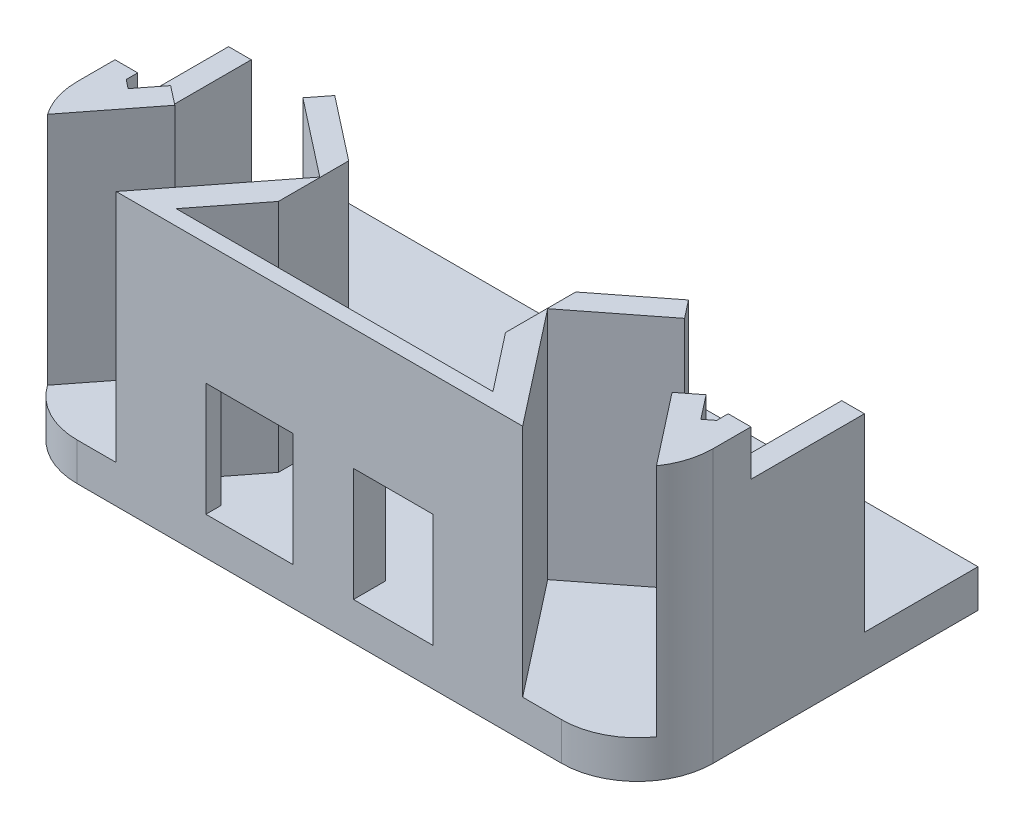
SolidWorks part; units mm, degrees
ref_plane "前视基准面" through (0, 0, 0) normal (0, 0, 1) x (1, 0, 0)
ref_plane "上视基准面" through (0, 0, 0) normal (0, 1, 0) x (1, 0, 0)
ref_plane "右视基准面" through (0, 0, 0) normal (1, 0, 0) x (0, 0, -1)
sketch "草图1" plane through (0, 0, 0) normal (0, 1, 0) x (1, 0, 0)
  line L1 (-42, 15) -> (42, 15)
  line L2 (-42, 15) -> (-42, -15)
  line L3 (-42, -15) -> (42, -15)
  line L4 (42, 15) -> (42, -15)
  line L5 (-42, 15) -> (42, -15) construction
  line L6 (-42, -15) -> (42, 15) construction
  point P0 (0, 0)
  dimension "D1" = 84
  dimension "D2" = 30
extrude "凸台-拉伸1" add sketch "草图1" along normal blind 34
sketch "草图2" plane through (0, 34, 0) normal (0, 1, 0) x (1, 0, 0)
  line L0 (-39, 15) -> (-3.1616, -13)
  line L1 (42, 15) -> (-42, 15) construction
  line L2 (-3.1616, -13) -> (3.1616, -13)
  line L3 (3.1616, -13) -> (39, 15)
  line L4 (-39, 15) -> (39, 15)
  line L5 (-42, 15) -> (-42, -15) construction
  line L6 (-42, -15) -> (42, -15) construction
  dimension "D1" = 38
  dimension "D2" = 3
  dimension "D3" = 3
  dimension "D4" = 2
  dimension "D5" = 38
extrude "切除-拉伸1" cut sketch "草图2" against normal blind 30
sketch "草图3" plane through (0, 34, 0) normal (0, 1, 0) x (1, 0, 0)
  line L0 (-26.357, 5.1222) -> (-42, -14.9)
  line L1 (42, -14.9) -> (26.357, 5.1222)
  line L2 (-39, 15) -> (-3.1616, -13) construction
  line L3 (42, -15) -> (42, 15) construction
  line L4 (-42, 15) -> (-42, -15) construction
  line L5 (-42, -14.9) -> (-42, -15)
  line L6 (0, 15) -> (0, -15) construction
  line L7 (3.1616, -13) -> (39, 15) construction
  line L8 (-42, -15) -> (-26.8499, -15)
  line L9 (-42, -15) -> (42, -15) construction
  line L10 (-26.8499, -15) -> (-16.9008, -2.2658)
  line L11 (-16.9008, -2.2658) -> (-26.357, 5.1222)
  line L12 (26.357, 5.1222) -> (16.9008, -2.2658)
  line L13 (16.9008, -2.2658) -> (26.8499, -15)
  line L14 (26.8499, -15) -> (42, -15)
  line L15 (42, -15) -> (42, -14.9)
  dimension "D1" = 12
  dimension "D2" = 0.1
  dimension "D3" = 12
  dimension "D4" = 0.1
sketch "草图4" plane through (0, 0, 15) normal (0, 0, 1) x (1, 0, 0)
  line L0 (0, 34) -> (0, 0) construction
  line L1 (-42, 34) -> (42, 34) construction
  line L2 (-15, 34) -> (-15, 16)
  line L3 (-15, 34) -> (15, 34)
  line L4 (0, 34) -> (0, 16)
  line L5 (-15, 16) -> (15, 16)
  line L6 (15, 34) -> (15, 16)
  line M3 (42, 34) -> (-42, 34)
  dimension "D1" = 18
  dimension "D2" = 15
extrude "切除-拉伸4" cut sketch "草图4" against normal blind 30 contours L2 L5 L4 L3 | L6 L4 L5 M3
extrude "切除-拉伸6" cut sketch "草图3" against normal blind 30
sketch "草图6" plane through (0, 4, 0) normal (0, 1, 0) x (1, 0, 0)
  line L0 (-24.51, 7.4862) -> (-15.0538, 0.0983)
  line L1 (-26.357, 5.1222) -> (-42, -14.9) construction
  line L2 (-26.8499, -15) -> (-16.9008, -2.2658) construction
  line L3 (-15.0538, 0.0983) -> (-13.2069, 2.4623)
  line L4 (-13.2069, 2.4623) -> (-22.663, 9.8502)
  line L5 (-22.663, 9.8502) -> (-24.51, 7.4862)
  line L6 (13.2069, 2.4623) -> (22.663, 9.8502)
  line L7 (16.9008, -2.2658) -> (26.8499, -15) construction
  line L8 (42, -14.9) -> (26.357, 5.1222) construction
  line L9 (22.663, 9.8502) -> (24.51, 7.4862)
  line L10 (42, -14.9) -> (26.357, 5.1222) construction
  line L11 (24.51, 7.4862) -> (15.0538, 0.0983)
  line L12 (16.9008, -2.2658) -> (26.8499, -15) construction
  line L13 (15.0538, 0.0983) -> (13.2069, 2.4623)
  line L17 (-39, 15) -> (-26.357, 5.1222) construction
  line L18 (26.357, 5.1222) -> (39, 15) construction
  dimension "D1" = 3
  dimension "D2" = 3
  dimension "D3" = 3
  dimension "D4" = 3
sketch "草图8" plane through (0, 34, 0) normal (0, 1, 0) x (1, 0, 0)
  line L0 (42, -14.9) -> (42, 15) construction
  line L1 (-39, 15) -> (39, 15)
  line L2 (-39, 15) -> (-39, -13)
  line L3 (-39, -13) -> (39, -13)
  line L4 (39, 15) -> (39, -13)
  line L5 (26.8499, -15) -> (42, -15) construction
  dimension "D1" = 3
  dimension "D2" = 2
extrude "切除-拉伸7" cut sketch "草图8" against normal blind 30
extrude "凸台-拉伸4" add sketch "草图6" along normal blind 30
sketch "草图9" plane through (0, 4, 0) normal (0, 1, 0) x (1, 0, 0)
  line L0 (-25.2873, -13) -> (-13.2069, 2.4623)
  line L1 (-13.2069, 2.4623) -> (-13.2069, -13)
  line L2 (-25.2873, -13) -> (25.2873, -13) construction
  line L3 (-13.2069, -13) -> (-24.5296, -13)
  line L4 (0, -13) -> (0, 15) construction
  line L5 (-15, -13) -> (15, -13) construction
  line L6 (39, 15) -> (-39, 15) construction
  line L7 (13.2069, -13) -> (24.5296, -13)
  line L8 (13.2069, 2.4623) -> (13.2069, -13)
  line L9 (25.2873, -13) -> (13.2069, 2.4623)
  line M4 (-13.2069, 2.4623) -> (-15.0538, 0.0983)
  line M14 (-25.2873, -13) -> (25.2873, -13)
  line M17 (15.0538, 0.0983) -> (13.2069, 2.4623)
extrude "凸台-拉伸5" add sketch "草图9" along normal blind 30 contours L9 L8 M14 M17 | L1 L0 M4 M14
sketch "草图11" plane through (0, 0, 13) normal (0, 0, 1) x (1, 0, 0)
  line L1 (-15, 34) -> (15, 34)
  line L2 (-15, 34) -> (-15, 16)
  line L3 (-15, 16) -> (15, 16)
  line L4 (15, 34) -> (15, 16)
extrude "切除-拉伸9" cut sketch "草图11" against normal through all
sketch "草图14" plane through (0, 34, 0) normal (0, 1, 0) x (1, 0, 0)
  line L0 (-20.9247, -13) -> (-15, -5.4167)
  line L1 (-15, 3.8633) -> (-15, -15) construction
  line L2 (-15, -5.4167) -> (-15, -13)
  line L3 (-15, -13) -> (-20.9247, -13)
  line L4 (-26.8499, -15) -> (-15, -15) construction
  line L5 (-26.8499, -15) -> (-15.0538, 0.0983) construction
  line L6 (-15, -5.4167) -> (-15, -13)
  line L7 (0, 15) -> (0, -15) construction
  line L8 (39, 15) -> (-39, 15) construction
  line L9 (-15, -15) -> (15, -15) construction
  line L10 (15, -5.4167) -> (15, -13)
  line L11 (15, -13) -> (20.9247, -13)
  line L12 (15, -5.4167) -> (15, -13)
  line L13 (20.9247, -13) -> (15, -5.4167)
  line M1 (-15, -15) -> (-15, 3.8633)
  dimension "D1" = 2
  dimension "D2" = 0
extrude "切除-拉伸12" cut sketch "草图14" against normal blind 30 contours L3 L0 M1 | L11 L13 L10
sketch "草图17" plane through (0, 4, 0) normal (0, 1, 0) x (1, 0, 0)
  line L0 (-22.663, 9.8502) -> (-23.3928, 10.4204)
  line L1 (-23.3928, 10.4204) -> (-25.2397, 8.0564)
  line L2 (-25.2397, 8.0564) -> (-24.51, 7.4862)
  line L3 (-24.51, 7.4862) -> (-22.663, 9.8502)
  line L4 (22.663, 9.8502) -> (23.3597, 10.3946)
  line L5 (23.3597, 10.3946) -> (25.2067, 8.0305)
  line L6 (25.2067, 8.0305) -> (24.51, 7.4862)
  line L7 (24.51, 7.4862) -> (22.663, 9.8502)
extrude "凸台-拉伸6" add sketch "草图17" along normal blind 30
sketch "草图23" plane through (0, 4, 0) normal (0, 1, 0) x (1, 0, 0)
  line L0 (23.3597, 10.3946) -> (26.1177, 12.5494)
  line L1 (26.1177, 12.5494) -> (32.2744, 4.6693)
  line L2 (32.2744, 4.6693) -> (29.7527, 2.6992)
  line L3 (29.7527, 2.6992) -> (25.4431, 8.2152)
  line L4 (25.4431, 8.2152) -> (25.2067, 8.0305)
  line L5 (25.2067, 8.0305) -> (23.3597, 10.3946)
  line L6 (0, 15) -> (0, -15) construction
  line L7 (39, 15) -> (-39, 15) construction
  line L8 (-15, -15) -> (15, -15) construction
  line L9 (-25.2067, 8.0305) -> (-23.3597, 10.3946)
  line L10 (-25.4431, 8.2152) -> (-25.2067, 8.0305)
  line L11 (-29.7527, 2.6992) -> (-25.4431, 8.2152)
  line L12 (-32.2744, 4.6693) -> (-29.7527, 2.6992)
  line L13 (-26.1177, 12.5494) -> (-32.2744, 4.6693)
  line L14 (-23.3597, 10.3946) -> (-26.1177, 12.5494)
  dimension "D1" = 3.5
  dimension "D2" = 10
  dimension "D3" = 90
extrude "凸台-拉伸9" add sketch "草图23" along normal blind 8
sketch "草图25" plane through (0, 34, 0) normal (0, 1, 0) x (1, 0, 0)
  line L0 (-25.4431, 8.2152) -> (-42, -12.9766)
  line L1 (-42, 15) -> (-42, -14.9) construction
  line L2 (-42, -12.9766) -> (-42, -14.9)
  line L3 (-42, -14.9) -> (-39, -11.0602)
  line L4 (-39, -11.0602) -> (-39, -9.1368)
  line L5 (-39, 15) -> (-39, -11.0602) construction
  line L6 (0, 15) -> (0, -15) construction
  line L7 (39, 15) -> (-39, 15) construction
  line L8 (-15, -15) -> (15, -15) construction
  line L9 (39, -11.0602) -> (39, -9.1368)
  line L10 (42, -14.9) -> (39, -11.0602)
  line L11 (42, -12.9766) -> (42, -14.9)
  line L12 (42, -12.9766) -> (39, -9.1368)
  line M1 (-39, -11.0602) -> (-39, 15)
  line M3 (-42, 15) -> (-42, -14.9)
  line M4 (-42, -14.9) -> (-39, -11.0602)
extrude "切除-拉伸16" cut sketch "草图25" against normal blind 30 contours L0 M1 M3 M4 | L11 L12 L9 L10
sketch "草图26" plane through (0, 4, 0) normal (0, 1, 0) x (1, 0, 0)
  line L0 (-39, -9.1368) -> (-35.306, -4.4088)
  line L1 (-35.306, -4.4088) -> (-39, -1.5227)
  line L2 (-39, 15) -> (-39, -9.1368) construction
  line L3 (-39, -1.5227) -> (-39, -9.1368)
  line L4 (0, 0) -> (0, -15) construction
  line L5 (-15, -15) -> (15, -15) construction
  line L6 (39, -1.5227) -> (39, -9.1368)
  line L7 (35.306, -4.4088) -> (39, -1.5227)
  line L8 (39, -9.1368) -> (35.306, -4.4088)
  line L9 (25.4431, 8.2152) -> (29.7527, 2.6992) construction
  dimension "D1" = 6
  dimension "D2" = 180
extrude "凸台-拉伸10" add sketch "草图26" along normal blind 30
sketch "草图27" plane through (0, 0, -15) normal (0, 0, -1) x (-1, 0, 0)
  line L0 (42, 34) -> (42, 0) construction
  line L1 (-42, 0) -> (42, 0)
  line L2 (-42, 0) -> (-42, 1)
  line L3 (-42, 1) -> (42, 1)
  line L4 (42, 0) -> (42, 1)
  dimension "D1" = 1
extrude "切除-拉伸17" cut sketch "草图27" against normal through all
sketch "草图28" plane through (0, 16, 0) normal (0, 1, 0) x (1, 0, 0)
  line L0 (-15, -15) -> (15, -15) construction
  line L1 (-13.2069, -13) -> (13.2069, -13)
  line L2 (-13.2069, -13) -> (-13.2069, -15)
  line L3 (-13.2069, -15) -> (13.2069, -15)
  line L4 (13.2069, -13) -> (13.2069, -15)
extrude "切除-拉伸18" cut sketch "草图28" against normal blind 12
sketch "草图29" plane through (-15, 0, 0) normal (1, 0, 0) x (0, 0, -1)
  line L1 (-13, 34) -> (-15, 34)
  line L2 (-13, 34) -> (-13, 16)
  line L3 (-13, 16) -> (-15, 16)
  line L4 (-15, 34) -> (-15, 16)
extrude "凸台-拉伸11" add sketch "草图29" along normal blind 30
sketch "草图30" plane through (0, 16, 0) normal (0, 1, 0) x (1, 0, 0)
  line L0 (-26.8499, -15) -> (26.8499, -15) construction
  line L1 (-15, 3.8633) -> (15, 3.8633)
  line L2 (-15, 3.8633) -> (-15, -15)
  line L3 (-15, -15) -> (15, -15)
  line L4 (15, 3.8633) -> (15, -15)
extrude "切除-拉伸19" cut sketch "草图30" against normal blind 12
sketch "草图31" plane through (0, 0, 15) normal (0, 0, 1) x (1, 0, 0)
  line L1 (-15, 16) -> (15, 16)
  line L2 (-15, 16) -> (-15, 19)
  line L3 (-15, 19) -> (15, 19)
  line L4 (15, 16) -> (15, 19)
extrude "切除-拉伸20" cut sketch "草图31" against normal blind 12
sketch "草图32" plane through (-42, 0, 0) normal (-1, 0, 0) x (0, 0, 1)
  line L1 (-15, 34) -> (0, 34)
  line L2 (-15, 34) -> (-15, 29)
  line L3 (-15, 29) -> (0, 29)
  line L4 (0, 34) -> (0, 29)
  dimension "D1" = 15
extrude "切除-拉伸21" cut sketch "草图32" against normal blind 10
sketch "草图33" plane through (42, 0, 0) normal (1, 0, 0) x (0, 0, -1)
  line L0 (-12.9766, 34) -> (15, 34) construction
  line L1 (15, 34) -> (0, 34)
  line L2 (15, 34) -> (15, 29)
  line L3 (15, 29) -> (0, 29)
  line L4 (0, 34) -> (0, 29)
  line L5 (15, 34) -> (15, 1) construction
  dimension "D1" = 15
extrude "切除-拉伸22" cut sketch "草图33" against normal blind 10
sketch "草图39" plane through (0, 0, -15) normal (0, 0, -1) x (-1, 0, 0)
  line L0 (0, 4) -> (0, 1) construction
  line L1 (-39, 4) -> (39, 4) construction
  line L2 (42, 1) -> (-42, 1) construction
  line L4 (-15, 4) -> (15, 4)
  line L5 (-15, 4) -> (-15, 1)
  line L6 (-15, 1) -> (15, 1)
  line L7 (15, 4) -> (15, 1)
  line L8 (-15, 4) -> (15, 1) construction
  line L9 (-15, 1) -> (15, 4) construction
  point P6 (0, 2.5)
extrude "凸台-拉伸12" add sketch "草图39" along normal blind 1
chamfer "倒角1" distance 10 angle 30 2 edges at (-15, 2.5, -15) (15, 2.5, -15) first distance on face at (-32, 11.3333, -15) first distance on face at (32, 11.3333, -15)
sketch "草图41" plane through (0, 4, 0) normal (0, 1, 0) x (1, 0, 0)
  line L0 (-32.2744, 4.6693) -> (-37.8277, -2.4386)
  line L1 (-35.306, -4.4088) -> (-39, -1.5227) construction
  line L2 (-37.8277, -2.4386) -> (-35.306, -4.4088)
  line L3 (-35.306, -4.4088) -> (-29.7527, 2.6992)
  line L4 (-29.7527, 2.6992) -> (-32.2744, 4.6693)
  line L5 (29.7527, 2.6992) -> (35.306, -4.4088)
  line L6 (32.2744, 4.6693) -> (37.8277, -2.4386)
  line L7 (39, -1.5227) -> (35.306, -4.4088) construction
  line L8 (37.8277, -2.4386) -> (35.306, -4.4088)
  line L9 (29.7527, 2.6992) -> (32.2744, 4.6693)
extrude "凸台-拉伸13" add sketch "草图41" along normal blind 8
sketch "草图42" plane through (0, 12, 0) normal (0, 1, 0) x (1, 0, 0)
  line L0 (35.306, -4.4088) -> (32.8434, -1.2567)
  line L1 (25.4431, 8.2152) -> (35.306, -4.4088) construction
  line L2 (32.8434, -1.2567) -> (35.365, 0.7134)
  line L3 (37.8277, -2.4386) -> (26.1177, 12.5494) construction
  line L4 (35.365, 0.7134) -> (37.8277, -2.4386)
  line L5 (39, -1.5227) -> (35.306, -4.4088) construction
  line L6 (35.306, -4.4088) -> (37.8277, -2.4386) construction
  line L7 (37.8277, -2.4386) -> (35.306, -4.4088)
  line L8 (0, 16) -> (0, 0) construction
  line L9 (-23.2679, 16) -> (23.2679, 16) construction
  line L10 (-37.8277, -2.4386) -> (-35.306, -4.4088)
  line L11 (-35.365, 0.7134) -> (-37.8277, -2.4386)
  line L12 (-32.8434, -1.2567) -> (-35.365, 0.7134)
  line L13 (-35.306, -4.4088) -> (-32.8434, -1.2567)
  dimension "D1" = 4
extrude "凸台-拉伸14" add sketch "草图42" along normal blind 22
fillet "圆角1" radius 10 2 edges at (42, 2.5, 15) (-42, 2.5, 15)
sketch "草图44" plane through (0, 4, 0) normal (0, 1, 0) x (1, 0, 0)
  line L0 (0, -15) -> (0, 16) construction
  line L1 (-15, -15) -> (15, -15) construction
  line L2 (-23.2679, 16) -> (23.2679, 16) construction
  line L4 (0, -15) -> (-3.5, -15)
  line L5 (0, -15) -> (0, -10.8)
  line L6 (0, -10.8) -> (-3.5, -10.8)
  line L7 (-3.5, -15) -> (-3.5, -10.8)
  line L8 (0, -15) -> (4.5, -15)
  line L9 (0, -15) -> (0, -10.8)
  line L10 (0, -10.8) -> (4.5, -10.8)
  line L11 (4.5, -15) -> (4.5, -10.8)
  line M24 (-15, -15) -> (15, -15)
  dimension "D1" = 4.2
  dimension "D2" = 4.5
  dimension "D3" = 3.5
extrude "凸台-拉伸16" add sketch "草图44" along normal blind 15 contours L7 L5 L6 M24 | L11 L10 L5 M24
sketch "草图46" plane through (0, 29, 0) normal (0, 1, 0) x (1, 0, 0)
  line L0 (32.8434, -1.2567) -> (40.2187, -10.6967) construction
  line L1 (42, -5) -> (42, 0) construction
  line L2 (42, 0) -> (39, 0) construction
  line L3 (39, 0) -> (39, -1.5227) construction
  line L4 (39, -1.5227) -> (37.8277, -2.4386) construction
  line L5 (37.8277, -2.4386) -> (35.365, 0.7134) construction
  line L6 (35.365, 0.7134) -> (32.8434, -1.2567) construction
  line L7 (15, -5.4167) -> (20.9247, -13) construction
  line L8 (20.9247, -13) -> (-20.9247, -13) construction
  line L9 (-20.9247, -13) -> (-15, -5.4167) construction
  line L10 (-15, -5.4167) -> (-15, 3.8633) construction
  line L11 (-15, 3.8633) -> (-23.3928, 10.4204) construction
  line L12 (-23.3928, 10.4204) -> (-25.2397, 8.0564) construction
  line L13 (-25.2397, 8.0564) -> (-15.0538, 0.0983) construction
  line L14 (-15.0538, 0.0983) -> (-26.8499, -15) construction
  line L15 (-26.8499, -15) -> (26.8499, -15) construction
  line L16 (26.8499, -15) -> (15.0538, 0.0983) construction
  line L17 (15.0538, 0.0983) -> (25.2067, 8.0305) construction
  line L18 (25.2067, 8.0305) -> (23.3597, 10.3946) construction
  line L19 (23.3597, 10.3946) -> (15, 3.8633) construction
  line L20 (15, 3.8633) -> (15, -5.4167) construction
  line L21 (-42, 0) -> (-42, -5) construction
  line L22 (-40.2187, -10.6967) -> (-32.8434, -1.2567) construction
  line L23 (-32.8434, -1.2567) -> (-35.365, 0.7134) construction
  line L24 (-35.365, 0.7134) -> (-37.8277, -2.4386) construction
  line L25 (-37.8277, -2.4386) -> (-39, -1.5227) construction
  line L26 (-39, -1.5227) -> (-39, 0) construction
  line L27 (-39, 0) -> (-42, 0) construction
  line L28 (32.8434, -1.2567) -> (40.2187, -10.6967)
  line L29 (42, -5) -> (42, 0)
  line L30 (42, 0) -> (39, 0)
  line L31 (39, 0) -> (39, -1.5227)
  line L32 (39, -1.5227) -> (37.8277, -2.4386)
  line L33 (37.8277, -2.4386) -> (35.365, 0.7134)
  line L34 (35.365, 0.7134) -> (32.8434, -1.2567)
  line L35 (15, -5.4167) -> (20.9247, -13)
  line L36 (20.9247, -13) -> (-20.9247, -13)
  line L37 (-20.9247, -13) -> (-15, -5.4167)
  line L38 (-15, -5.4167) -> (-15, 3.8633)
  line L39 (-15, 3.8633) -> (-23.3928, 10.4204)
  line L40 (-23.3928, 10.4204) -> (-25.2397, 8.0564)
  line L41 (-25.2397, 8.0564) -> (-15.0538, 0.0983)
  line L42 (-15.0538, 0.0983) -> (-26.8499, -15)
  line L43 (-26.8499, -15) -> (26.8499, -15)
  line L44 (26.8499, -15) -> (15.0538, 0.0983)
  line L45 (15.0538, 0.0983) -> (25.2067, 8.0305)
  line L46 (25.2067, 8.0305) -> (23.3597, 10.3946)
  line L47 (23.3597, 10.3946) -> (15, 3.8633)
  line L48 (15, 3.8633) -> (15, -5.4167)
  line L49 (-42, 0) -> (-42, -5)
  line L50 (-40.2187, -10.6967) -> (-32.8434, -1.2567)
  line L51 (-32.8434, -1.2567) -> (-35.365, 0.7134)
  line L52 (-35.365, 0.7134) -> (-37.8277, -2.4386)
  line L53 (-37.8277, -2.4386) -> (-39, -1.5227)
  line L54 (-39, -1.5227) -> (-39, 0)
  line L55 (-39, 0) -> (-42, 0)
  arc A0 (40.2187, -10.6967) -> (42, -5) centre (32, -5) ccw construction
  arc A1 (-42, -5) -> (-40.2187, -10.6967) centre (-32, -5) ccw construction
  arc A2 (40.2187, -10.6967) -> (42, -5) centre (32, -5) ccw
  arc A3 (-42, -5) -> (-40.2187, -10.6967) centre (-32, -5) ccw
sketch "草图47" plane through (0, 34, 0) normal (0, 1, 0) x (1, 0, 0)
  line L0 (32.8434, -1.2567) -> (40.2187, -10.6967) construction
  line L1 (42, -5) -> (42, 0) construction
  line L2 (42, 0) -> (39, 0) construction
  line L3 (39, 0) -> (39, -1.5227) construction
  line L4 (39, -1.5227) -> (37.8277, -2.4386) construction
  line L5 (37.8277, -2.4386) -> (35.365, 0.7134) construction
  line L6 (35.365, 0.7134) -> (32.8434, -1.2567) construction
  line L7 (-42, 0) -> (-42, -5) construction
  line L8 (-40.2187, -10.6967) -> (-32.8434, -1.2567) construction
  line L9 (-32.8434, -1.2567) -> (-35.365, 0.7134) construction
  line L10 (-35.365, 0.7134) -> (-37.8277, -2.4386) construction
  line L11 (-37.8277, -2.4386) -> (-39, -1.5227) construction
  line L12 (-39, -1.5227) -> (-39, 0) construction
  line L13 (-39, 0) -> (-42, 0) construction
  line L14 (15, -5.4167) -> (20.9247, -13) construction
  line L15 (20.9247, -13) -> (-20.9247, -13) construction
  line L16 (-20.9247, -13) -> (-15, -5.4167) construction
  line L17 (-15, -5.4167) -> (-15, 3.8633) construction
  line L18 (-15, 3.8633) -> (-23.3928, 10.4204) construction
  line L19 (-23.3928, 10.4204) -> (-25.2397, 8.0564) construction
  line L20 (-25.2397, 8.0564) -> (-15.0538, 0.0983) construction
  line L21 (-15.0538, 0.0983) -> (-26.8499, -15) construction
  line L22 (-26.8499, -15) -> (26.8499, -15) construction
  line L23 (26.8499, -15) -> (15.0538, 0.0983) construction
  line L24 (15.0538, 0.0983) -> (25.2067, 8.0305) construction
  line L25 (25.2067, 8.0305) -> (23.3597, 10.3946) construction
  line L26 (23.3597, 10.3946) -> (15, 3.8633) construction
  line L27 (15, 3.8633) -> (15, -5.4167) construction
  line L28 (32.8434, -1.2567) -> (40.2187, -10.6967)
  line L29 (42, -5) -> (42, 0)
  line L30 (42, 0) -> (39, 0)
  line L31 (39, 0) -> (39, -1.5227)
  line L32 (39, -1.5227) -> (37.8277, -2.4386)
  line L33 (37.8277, -2.4386) -> (35.365, 0.7134)
  line L34 (35.365, 0.7134) -> (32.8434, -1.2567)
  line L35 (-42, 0) -> (-42, -5)
  line L36 (-40.2187, -10.6967) -> (-32.8434, -1.2567)
  line L37 (-32.8434, -1.2567) -> (-35.365, 0.7134)
  line L38 (-35.365, 0.7134) -> (-37.8277, -2.4386)
  line L39 (-37.8277, -2.4386) -> (-39, -1.5227)
  line L40 (-39, -1.5227) -> (-39, 0)
  line L41 (-39, 0) -> (-42, 0)
  line L42 (15, -5.4167) -> (20.9247, -13)
  line L43 (20.9247, -13) -> (-20.9247, -13)
  line L44 (-20.9247, -13) -> (-15, -5.4167)
  line L45 (-15, -5.4167) -> (-15, 3.8633)
  line L46 (-15, 3.8633) -> (-23.3928, 10.4204)
  line L47 (-23.3928, 10.4204) -> (-25.2397, 8.0564)
  line L48 (-25.2397, 8.0564) -> (-15.0538, 0.0983)
  line L49 (-15.0538, 0.0983) -> (-26.8499, -15)
  line L50 (-26.8499, -15) -> (26.8499, -15)
  line L51 (26.8499, -15) -> (15.0538, 0.0983)
  line L52 (15.0538, 0.0983) -> (25.2067, 8.0305)
  line L53 (25.2067, 8.0305) -> (23.3597, 10.3946)
  line L54 (23.3597, 10.3946) -> (15, 3.8633)
  line L55 (15, 3.8633) -> (15, -5.4167)
  arc A0 (40.2187, -10.6967) -> (42, -5) centre (32, -5) ccw construction
  arc A1 (-42, -5) -> (-40.2187, -10.6967) centre (-32, -5) ccw construction
  arc A2 (40.2187, -10.6967) -> (42, -5) centre (32, -5) ccw
  arc A3 (-42, -5) -> (-40.2187, -10.6967) centre (-32, -5) ccw
extrude "凸台-拉伸17" add sketch "草图47" along normal blind 1
sketch "草图50" plane through (0, 1, 0) normal (0, -1, 0) x (1, 0, 0)
  line L8 (42, -15) -> (42, 5)
  line L9 (32, 15) -> (-32, 15)
  line L10 (-42, 5) -> (-42, -15)
  line L11 (-42, -15) -> (-25, -15)
  line L12 (-42, -15) -> (-25, -15)
  line L13 (-25, -15) -> (-23.2679, -16)
  line L14 (-25, -15) -> (-23.2679, -16)
  line L15 (-23.2679, -16) -> (23.2679, -16)
  line L16 (42, -15) -> (42, 5)
  line L17 (32, 15) -> (-32, 15)
  line L18 (-42, 5) -> (-42, -15)
  line L24 (-23.2679, -16) -> (23.2679, -16)
  line L25 (23.2679, -16) -> (25, -15)
  line L26 (23.2679, -16) -> (25, -15)
  line L27 (25, -15) -> (42, -15)
  line L28 (25, -15) -> (42, -15)
  arc A2 (42, 5) -> (32, 15) centre (32, 5) ccw
  arc A3 (-32, 15) -> (-42, 5) centre (-32, 5) ccw
  arc A4 (42, 5) -> (32, 15) centre (32, 5) ccw
  arc A5 (-32, 15) -> (-42, 5) centre (-32, 5) ccw
  dimension "D1" = 0
extrude "凸台-拉伸20" add sketch "草图50" along normal blind 2
sketch "草图51" plane through (0, 4, 0) normal (0, 1, 0) x (1, 0, 0)
  line L0 (-42, 15) -> (-25, 15)
  line L1 (-25, 15) -> (-23.2679, 16)
  line L2 (-23.2679, 16) -> (23.2679, 16)
  line L3 (23.2679, 16) -> (25, 15)
  line L4 (25, 15) -> (42, 15)
  line L5 (42, 15) -> (42, 30)
  line L6 (42, 30) -> (-42, 30)
  line L7 (-42, 30) -> (-42, 15)
  dimension "D1" = 15
extrude "凸台-拉伸21" add sketch "草图51" against normal blind 5
sketch "草图52" plane through (0, -1, 0) normal (0, -1, 0) x (1, 0, 0)
  circle A0 centre (35, -17) radius 1.75
  circle A1 centre (9, -23) radius 1.75
  circle A2 centre (-9, -23) radius 1.75
  circle A3 centre (-35, -17) radius 1.75
extrude "切除-拉伸23" cut sketch "草图52" against normal blind 10
